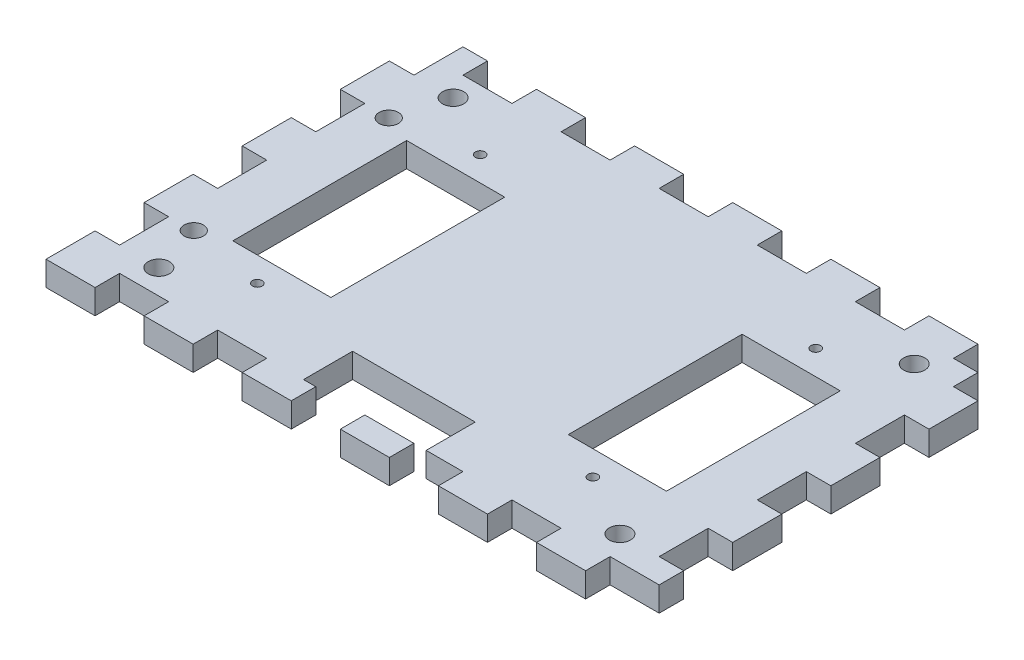
SolidWorks part; units mm, degrees
note: The reader was unsure of these and kept them because the rebuilt part matched: shared geometry of "Sketch2<4>".
material "Delrin 2700 NC010, Low Viscosity Acetal Copolymer (SS)"
ref_plane "Front Plane" through (0, 0, 0) normal (0, 0, 1) x (1, 0, 0)
ref_plane "Top Plane" through (0, 0, 0) normal (0, 1, 0) x (1, 0, 0)
ref_plane "Right Plane" through (0, 0, 0) normal (1, 0, 0) x (0, 0, -1)
sketch "Sketch1" plane through (0, 0, 0) normal (0, 1, 0) x (1, 0, 0)
  line L1 (0, 0) -> (152.4, 0)
  line L2 (0, 0) -> (0, 101.6)
  line L3 (0, 101.6) -> (152.4, 101.6)
  line L4 (152.4, 0) -> (152.4, 101.6)
  dimension "D3" = 101.6
  dimension "D5" = 152.4
extrude "Boss-Extrude2" add sketch "Sketch1" along normal blind 6.35
ref_plane "Plane1" through (76.2, 0, 0) normal (-1, 0, 0) x (0, 0, 1)
ref_plane "Plane2" through (0, 0, -50.8) normal (0, 0, -1) x (-1, 0, 0)
sketch "Sketch2" plane through (0, 6.35, 0) normal (0, 1, 0) x (1, 0, 0)
  line L0 (6.35, 101.6) -> (6.35, 0)
  line L1 (12.7, 101.6) -> (12.7, 95.25)
  line L2 (0, 0) -> (152.4, 0) construction
  line L3 (0, 95.25) -> (152.4, 95.25)
  line L4 (25.4, 101.6) -> (25.4, 95.25)
  line L5 (152.4, 0) -> (152.4, 101.6) construction
  line L6 (0, 0) -> (0, 101.6) construction
  line L7 (0, 101.6) -> (152.4, 101.6) construction
  line L8 (0, 12.7) -> (6.35, 12.7)
  line L17 (0, 25.4) -> (6.35, 25.4)
  line L18 (0, 38.1) -> (6.35, 38.1)
  line L19 (0, 50.8) -> (6.35, 50.8)
  line L20 (0, 0) -> (152.4, 0)
  line L21 (152.4, 0) -> (152.4, 101.6)
  line L22 (152.4, 101.6) -> (0, 101.6)
  line L23 (0, 101.6) -> (0, 0)
  line L24 (0, 0) -> (152.4, 0)
  line L25 (152.4, 0) -> (152.4, 101.6)
  line L26 (152.4, 101.6) -> (0, 101.6)
  line L27 (0, 101.6) -> (0, 0)
  line L28 (0, 63.5) -> (6.35, 63.5)
  line L29 (0, 76.2) -> (6.35, 76.2)
  line L30 (0, 88.9) -> (6.35, 88.9)
  line L31 (0, 101.6) -> (6.35, 101.6)
  line L32 (38.1, 101.6) -> (38.1, 95.25)
  line L33 (50.8, 101.6) -> (50.8, 95.25)
  line L34 (63.5, 101.6) -> (63.5, 95.25)
  line L35 (76.2, 101.6) -> (76.2, 95.25)
  line L36 (88.9, 101.6) -> (88.9, 95.25)
  line L37 (101.6, 101.6) -> (101.6, 95.25)
  line L38 (114.3, 101.6) -> (114.3, 95.25)
  line L39 (127, 101.6) -> (127, 95.25)
  line L40 (139.7, 101.6) -> (139.7, 95.25)
  line L41 (152.4, 101.6) -> (152.4, 95.25)
  line L42 (165.1, 101.6) -> (165.1, 95.25)
  dimension "D1" = 6.35
  dimension "D2" = 6.35
  dimension "D4" = 12.7
  dimension "D6" = 12.7
  dimension "D7" = 12.7
  dimension "D5" = 8
extrude "Cut-Extrude2" cut sketch "Sketch2" against normal blind 6.35
mirror "Mirror1" about plane through (76.2, 0, 0) normal (-1, 0, 0) of "Cut-Extrude2"
extrude "Cut-Extrude3" cut sketch "Sketch2<4>" against normal blind 6.35
sketch "Sketch2<4>" plane through (0, 6.35, 0) normal (0, 1, 0) x (1, 0, 0) same geometry as "Sketch2"
mirror "Mirror2" about plane through (0, 0, -50.8) normal (0, 0, -1) of "Cut-Extrude3"
hole_wizard "Ø5.0mm Dowel Hole1" [suppressed] positions "Sketch3" profile "Sketch4" hole size "Ø5.0" standard "ANSI Metric"
sketch "Sketch3" plane through (0, 6.35, 0) normal (0, 1, 0) x (1, 0, 0)
  line L0 (0, 29.526) -> (152.4, 29.526) construction
  line L1 (0, 25.4) -> (0, 38.1) construction
  line L2 (152.4, 25.4) -> (152.4, 38.1) construction
  line L4 (63.5, 6.35) -> (76.2, 6.35) construction
  point P0 (76.2, 31.75)
  point P12 (76.2, 29.526)
  dimension "D1" = 25.4
sketch "Sketch4" plane through (76.2, 6.35, -31.75) normal (1, 0, 0) x (0, 0, 1)
  line L0 (0, 0) -> (0, 6.35)
  line L1 (0, 6.35) -> (2.5, 6.35)
  line L2 (2.5, 6.35) -> (2.5, 0)
  line L5 (2.5, 0) -> (0, 0)
  line L11 (0, -6.35) -> (0, 107.95) construction
  dimension "Thru Hole Dia." = 5
  dimension "Thru Hole Depth" = 6.35
hole_wizard "Ø3.0mm Dowel Hole1" [suppressed] positions "Sketch5" profile "Sketch6" hole size "Ø3.0" standard "ANSI Metric"
sketch "Sketch5" plane through (0, 0, 0) normal (0, -1, 0) x (-1, 0, 0)
  point P0 (-60.7, 47.25)
  point P3 (-91.7, 47.25)
  point P6 (-91.7, 16.25)
  point P9 (-60.7, 16.25)
sketch "Sketch6" plane through (60.7, 0, -47.25) normal (1, 0, 0) x (0, 0, -1)
  line L0 (0, 0) -> (0, 6.35)
  line L1 (0, 6.35) -> (1.5, 6.35)
  line L2 (1.5, 6.35) -> (1.5, 0)
  line L5 (1.5, 0) -> (0, 0)
  line L11 (0, -6.35) -> (0, 107.95) construction
  dimension "Thru Hole Dia." = 3
  dimension "Thru Hole Depth" = 6.35
hole_wizard "Ø5.0mm Dowel Hole2" [suppressed] positions "Sketch7" profile "Sketch8" hole size "Ø5.0" standard "ANSI Metric"
sketch "Sketch7" plane through (0, 6.35, 0) normal (0, 1, 0) x (1, 0, 0)
  line L0 (0, 88.9) -> (152.4, 88.9) construction
  line L1 (0, 76.2) -> (0, 88.9) construction
  line L2 (152.4, 76.2) -> (152.4, 88.9) construction
  line L4 (6.35, 101.6) -> (12.7, 101.6) construction
  point P0 (32.766, 88.9)
  point P17 (119.634, 88.9)
  point P19 (76.2, 88.9)
  dimension "D1" = 12.7
  dimension "D2" = 43.434
  dimension "D3" = 43.434
sketch "Sketch8" plane through (32.766, 6.35, -88.9) normal (1, 0, 0) x (0, 0, 1)
  line L0 (0, 0) -> (0, 6.35)
  line L1 (0, 6.35) -> (2.5, 6.35)
  line L2 (2.5, 6.35) -> (2.5, 0)
  line L5 (2.5, 0) -> (0, 0)
  line L11 (0, -6.35) -> (0, 107.95) construction
  dimension "Thru Hole Dia." = 5
  dimension "Thru Hole Depth" = 6.35
sketch "Sketch9" plane through (0, 6.35, 0) normal (0, 1, 0) x (1, 0, 0)
  line L0 (0, 50.8) -> (152.4, 50.8) construction
  line L1 (20.066, 73.3) -> (45.466, 73.3)
  line L2 (20.066, 73.3) -> (20.066, 28.3)
  line L3 (20.066, 28.3) -> (45.466, 28.3)
  line L4 (45.466, 73.3) -> (45.466, 28.3)
  line L8 (76.2, 0) -> (76.2, 101.6) construction
  line L15 (132.334, 28.3) -> (106.934, 28.3)
  line L16 (106.934, 73.3) -> (106.934, 28.3)
  line L17 (132.334, 73.3) -> (106.934, 73.3)
  line L18 (132.334, 73.3) -> (132.334, 28.3)
  point P8 (32.766, 73.3)
  point P12 (45.466, 50.8)
  point P15 (76.2, 50.8)
  dimension "D2" = 43.434
  dimension "D1" = 25.4
  dimension "D3" = 45
extrude "Cut-Extrude4" cut sketch "Sketch9" against normal through all
sketch "Sketch11" [suppressed] plane through (0, 6.35, 0) normal (0, 1, 0) x (1, 0, 0)
  line L0 (76.2, 88.9) -> (76.2, 57.15) construction
  line L1 (78.7, 88.9) -> (78.7, 57.15)
  line L2 (73.7, 88.9) -> (73.7, 57.15)
  line L3 (76.2, 101.6) -> (76.2, 95.25) construction
  line L5 (76.2, 0) -> (88.9, 0) construction
  arc A0 (78.7, 88.9) -> (73.7, 88.9) centre (76.2, 88.9) ccw
  arc A1 (73.7, 57.15) -> (78.7, 57.15) centre (76.2, 57.15) ccw
  point P2 (76.2, 73.025)
  dimension "D2" = 2.5
  dimension "D1" = 31.75
  dimension "D3" = 57.15
extrude "Cut-Extrude5" [suppressed] cut sketch "Sketch11" against normal through all
sketch "Sketch12" plane through (0, 6.35, 0) normal (0, 1, 0) x (1, 0, 0)
  line L0 (63.5, 6.35) -> (76.2, 6.35) construction
  line L1 (60.325, 19.05) -> (92.075, 19.05)
  line L2 (60.325, 19.05) -> (60.325, 6.35)
  line L3 (60.325, 6.35) -> (92.075, 6.35)
  line L4 (92.075, 19.05) -> (92.075, 6.35)
  line L6 (76.2, 101.6) -> (76.2, 95.25) construction
  point P8 (76.2, 19.05)
  dimension "D1" = 31.75
  dimension "D2" = 12.7
extrude "Cut-Extrude6" cut sketch "Sketch12" against normal through all
hole_wizard "Tap Drill for M3x0.5 Tap1" positions "Sketch16" profile "Sketch17" hole size "M3x0.5" standard "ANSI Metric" end condition through all
sketch "Sketch16" plane through (0, 6.35, 0) normal (0, 1, 0) x (1, 0, 0)
  line L0 (45.466, 73.3) -> (20.066, 73.3) construction
  line L1 (132.334, 73.3) -> (106.934, 73.3) construction
  line L3 (32.766, 79.65) -> (119.634, 79.65) construction
  line L4 (32.766, 79.65) -> (32.766, 21.95) construction
  line L5 (32.766, 21.95) -> (119.634, 21.95) construction
  line L6 (119.634, 79.65) -> (119.634, 21.95) construction
  line L7 (45.466, 28.3) -> (45.466, 73.3) construction
  point P0 (32.766, 79.65)
  point P2 (32.766, 21.95)
  point P4 (119.634, 21.95)
  point P6 (119.634, 79.65)
  point P11 (32.766, 73.3)
  point P14 (119.634, 73.3)
  point P164 (45.466, 50.8)
  point P165 (32.766, 50.8)
  dimension "D1" = 6.35
sketch "Sketch17" plane through (32.766, 6.35, -79.65) normal (1, 0, 0) x (0, 0, 1)
  line L0 (0, 0) -> (0, 6.35)
  line L1 (0, 6.35) -> (1.25, 6.35)
  line L2 (1.25, 6.35) -> (1.25, 0)
  line L5 (1.25, 0) -> (0, 0)
  line L11 (0, -6.35) -> (0, 107.95) construction
  dimension "Thru Hole Dia." = 2.5
  dimension "Thru Hole Depth" = 6.35
hole_wizard "M5 Clearance Hole1" positions "Sketch18" profile "Sketch19" hole size "M5" standard "ANSI Metric" end condition through all
sketch "Sketch18" plane through (0, 6.35, 0) normal (0, 1, 0) x (1, 0, 0)
  line L1 (16.51, 12.7) -> (135.89, 12.7)
  line L2 (16.51, 12.7) -> (16.51, 88.9)
  line L3 (16.51, 88.9) -> (135.89, 88.9)
  line L4 (135.89, 12.7) -> (135.89, 88.9)
  line L5 (76.2, 3.4925) -> (76.2, -3.4925) construction
  line L6 (3.4925, 50.8) -> (-3.4925, 50.8) construction
  point P0 (16.51, 88.9)
  point P2 (135.89, 88.9)
  point P4 (135.89, 12.7)
  point P6 (16.51, 12.7)
  point P236 (76.2, 88.9)
  point P239 (16.51, 50.8)
  dimension "D1" = 76.2
  dimension "D2" = 119.38
sketch "Sketch19" plane through (16.51, 6.35, -88.9) normal (1, 0, 0) x (0, 0, 1)
  line L0 (0, 0) -> (0, 6.35)
  line L1 (0, 6.35) -> (2.75, 6.35)
  line L2 (2.75, 6.35) -> (2.75, 0)
  line L5 (2.75, 0) -> (0, 0)
  line L11 (0, -6.35) -> (0, 107.95) construction
  dimension "Thru Hole Dia." = 5.5
  dimension "Thru Hole Depth" = 6.35
hole_wizard "Ø5.0mm Dowel Hole3" positions "Sketch20" profile "Sketch21" hole size "Ø5.0" standard "ANSI Metric" end condition through all
sketch "Sketch20" plane through (0, 0, 0) normal (0, -1, 0) x (-1, 0, 0)
  point P0 (-12.7, 76.04)
  point P2 (-12.7, 25.56)
sketch "Sketch21" plane through (12.7, 0, -76.04) normal (1, 0, 0) x (0, 0, -1)
  line L0 (0, 0) -> (0, 6.35)
  line L1 (0, 6.35) -> (2.5, 6.35)
  line L2 (2.5, 6.35) -> (2.5, 0)
  line L5 (2.5, 0) -> (0, 0)
  line L11 (0, -6.35) -> (0, 107.95) construction
  dimension "Thru Hole Dia." = 5
  dimension "Thru Hole Depth" = 6.35
hole_wizard "Ø5.0mm Dowel Hole4" [suppressed] positions "Sketch27" profile "Sketch28" hole size "Ø5.0" standard "ANSI Metric"
sketch "Sketch27" plane through (0, 0, 0) normal (0, -1, 0) x (-1, 0, 0)
  line L0 (-152.4, 12.7) -> (0, 12.7) construction
  line L3 (-152.4, 76.2) -> (-152.4, 88.9) construction
  line L4 (0, 76.2) -> (0, 88.9) construction
  line L5 (-127, 0) -> (-139.7, 0) construction
  point P0 (-119.634, 12.7)
  point P2 (-32.766, 12.7)
  point P11 (-76.2, 12.7)
  dimension "D1" = 12.7
  dimension "D2" = 43.434
  dimension "D3" = 43.434
sketch "Sketch28" plane through (119.634, 0, -12.7) normal (1, 0, 0) x (0, 0, -1)
  line L0 (0, 0) -> (0, 6.35)
  line L1 (0, 6.35) -> (2.5, 6.35)
  line L2 (2.5, 6.35) -> (2.5, 0)
  line L5 (2.5, 0) -> (0, 0)
  line L11 (0, -6.35) -> (0, 107.95) construction
  dimension "Thru Hole Dia." = 5
  dimension "Thru Hole Depth" = 6.35
equation "\"acrillic thickness\"= 1 / 4"
equation "\"D1@Sketch2\"=\"acrillic thickness\""
equation "\"D2@Sketch2\"=\"acrillic thickness\""
equation "\"film hole spacing\"= 0.1866"
equation "\"drive cog diamiter\"= 1"
equation "\"bushing diamiter\"= 1 / 8"
equation "\"D1@Sketch7\"=\"drive cog diamiter\"/2"
equation "\"D1@Sketch9\"=\"drive cog diamiter\""
equation "\"holes between cogs\"= 18"
equation "\"D2@Sketch7\"=\"film hole spacing\"*\"holes between cogs\"/2"
equation "\"D3@Sketch7\"=\"film hole spacing\"*\"holes between cogs\"/2"
equation "\"D2@Sketch9\"=\"film hole spacing\"*\"holes between cogs\"/2"
equation "\"wrench width\"= 0.5 * 2"
equation "\"D1@Sketch12\"=\"wrench width\"*1.25"
equation "\"D2@Sketch27\"=\"holes between cogs\"*\"film hole spacing\"/2"
equation "\"D3@Sketch27\"=\"holes between cogs\"*\"film hole spacing\"/2"
